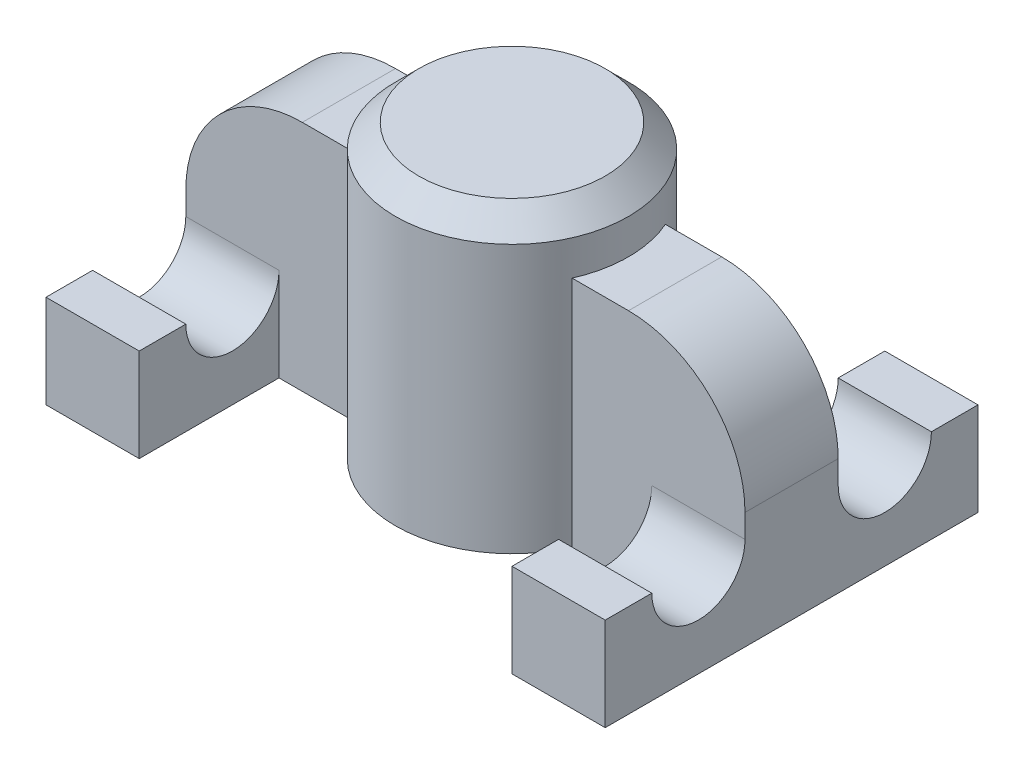
SolidWorks part; units mm, degrees
ref_plane "Front Plane" through (0, 0, 0) normal (0, 0, 1) x (1, 0, 0)
ref_plane "Top Plane" through (0, 0, 0) normal (0, 1, 0) x (1, 0, 0)
ref_plane "Right Plane" through (0, 0, 0) normal (1, 0, 0) x (0, 0, -1)
sketch "Sketch1" plane through (0, 0, 0) normal (0, 1, 0) x (1, 0, 0)
  circle A0 centre (0, 0) radius 10
  dimension "D1" = 20
extrude "Pen Cap" add sketch "Sketch1" along normal blind 25
sketch "Sketch2" plane through (0, 0, 0) normal (0, -1, 0) x (1, 0, 0)
  line L1 (-24, 4) -> (24, 4)
  line L2 (-24, 4) -> (-24, -4)
  line L3 (-24, -4) -> (24, -4)
  line L4 (24, 4) -> (24, -4)
  point P4 (0, 4)
  point P6 (-24, 0)
  dimension "D1" = 8
  dimension "D2" = 48
extrude "Hook Structure" add sketch "Sketch2" against normal blind 20
hole_wizard "Pen Centering Hole" positions "Sketch4" profile "Sketch3" legacy
sketch "Sketch4" plane through (0, 0, 0) normal (0, -1, 0) x (1, 0, 0)
  point P0 (0, 0)
sketch "Sketch3" plane through (0, 0, 0) normal (1, 0, 0) x (0, 0, -1)
  line L0 (0, 0) -> (0, 21.25)
  line L1 (0, 21.25) -> (6.25, 15)
  line L2 (6.25, 15) -> (6.25, 0)
  line L4 (6.25, 0) -> (0, 0)
  line L6 (0, 21.25) -> (-6.25, 15) construction
  line L7 (0, -4.2442) -> (0, 117.3081) construction
  dimension "Diameter" = 12.5
  dimension "Depth" = 15
  dimension "Drill Angle" = 90
sketch "Sketch6" plane through (24, 0, 0) normal (1, 0, 0) x (0, 0, -1)
  line L0 (-4, 0) -> (-16, 0)
  line L1 (-16, 0) -> (-16, 8)
  line L2 (-16, 8) -> (-12, 8)
  line L3 (-4, 0) -> (-4, 20) construction
  line L4 (-4, 8) -> (-4, 0)
  line L5 (0, 0) -> (0, 20) construction
  line L6 (4, 20) -> (-4, 20) construction
  line L7 (4, 8) -> (4, 0)
  line L8 (16, 8) -> (12, 8)
  line L9 (16, 0) -> (16, 8)
  line L10 (4, 0) -> (16, 0)
  arc A0 (-12, 8) -> (-4, 8) centre (-8, 8) ccw
  arc A1 (12, 8) -> (4, 8) centre (8, 8) cw
  dimension "D2" = 4
  dimension "D1" = 8
  dimension "D3" = 12
extrude "Hooks" add sketch "Sketch6" against normal blind 8
mirror "Hook Mirror" about plane through (0, 0, 0) normal (1, 0, 0) of "Hooks"
fillet "Corner Dec" radius 10 2 edges at (24, 20, 0) (-24, 20, 0)
chamfer "Chamfer1" distance 2 angle 45 1 edges at (0, 25, 10)
